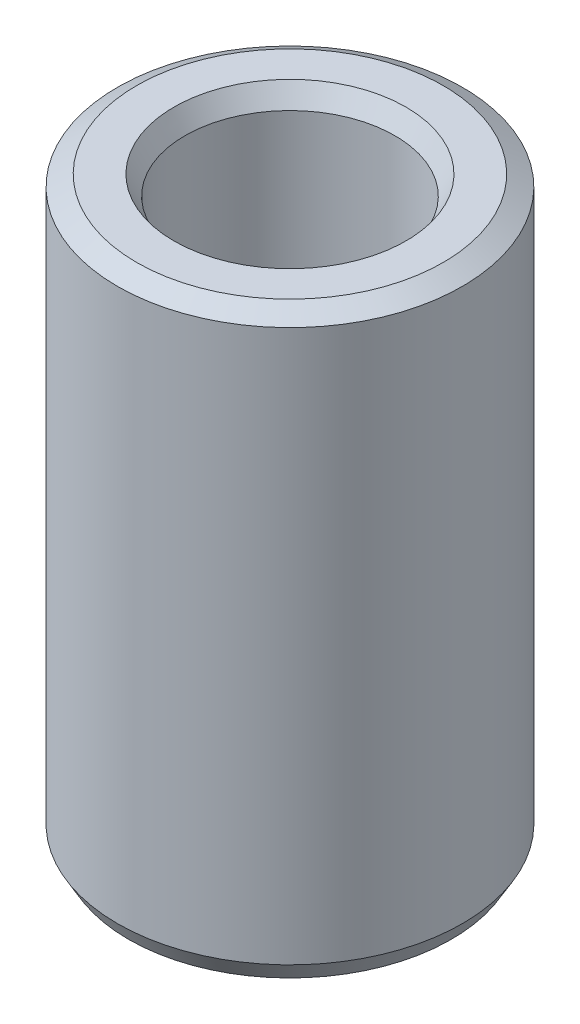
SolidWorks part; units mm, degrees
ref_plane "Front Plane" through (0, 0, 0) normal (0, 0, 1) x (1, 0, 0)
ref_plane "Top Plane" through (0, 0, 0) normal (0, 1, 0) x (1, 0, 0)
ref_plane "Right Plane" through (0, 0, 0) normal (1, 0, 0) x (0, 0, -1)
sketch "Sketch1" plane through (0, 0, 0) normal (0, 1, 0) x (1, 0, 0)
  circle A0 centre (0, 0) radius 42.5
  dimension "SLEEVE_OD" = 85
extrude "Boss-Extrude1" add sketch "Sketch1" along normal blind 143.4565
sketch "Sketch2" plane through (0, 0, 0) normal (0, 1, 0) x (1, 0, 0)
  circle A0 centre (0, 0) radius 25.8542
  dimension "BORE_D" = 51.7083
extrude "Cut-Extrude1" cut sketch "Sketch2" along normal through all
chamfer "Chamfer1" distance 2.732 angle 60 4 edges at (0, 143.4565, 25.8542) (0, 0, 25.8542) (0, 0, 42.5) (0, 143.4565, 42.5) first distance on face at (0, 143.4565, 25.8542) first distance on face at (0, 0, 25.8542) first distance on face at (0, 143.4565, 42.5)
